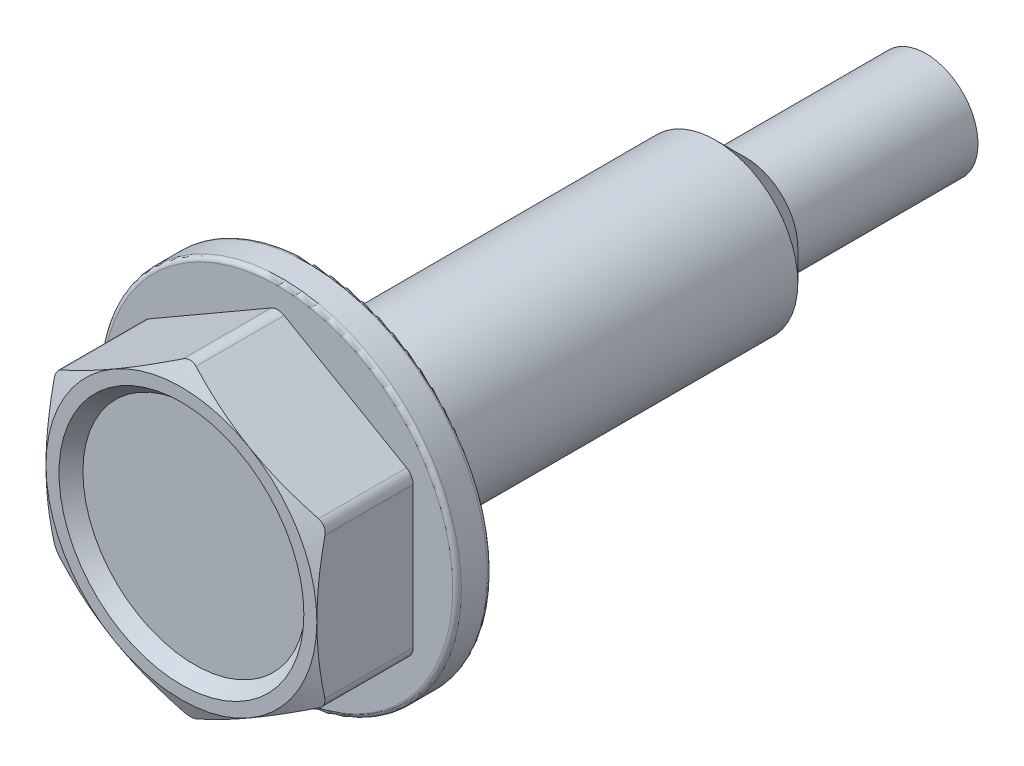
SolidWorks part; units mm, degrees
ref_plane "Front Plane" through (0, 0, 0) normal (0, 0, 1) x (1, 0, 0)
ref_plane "Top Plane" through (0, 0, 0) normal (0, 1, 0) x (1, 0, 0)
ref_plane "Right Plane" through (0, 0, 0) normal (1, 0, 0) x (0, 0, -1)
sketch "Sketch2" plane through (0, 0, 0) normal (0, 0, 1) x (1, 0, 0)
  circle A0 centre (0, 0) radius 2.413
  dimension "screw dia" = 4.826
curve "Helix/Spiral1" pitch 1.5875 height 25.4 radius 2.413 centre (0, 0, 0) axis (0, 0, 1) start towards (0, 1, 0) parameters "TPI LENGTH"=25.4, "PITCH"=1.5875
sketch "Sketch3" plane through (0, 0, 0) normal (1, 0, 0) x (0, 0, -1)
  line L0 (0.113, 2.413) -> (-0.113, 2.413)
  line L1 (-0.113, 2.413) -> (-0.6236, 1.5287)
  line L2 (-0.6236, 1.5287) -> (0.6236, 1.5287)
  line L3 (0.6236, 1.5287) -> (0.113, 2.413)
  line L4 (0, 0) -> (0, 2.413) construction
  line L5 (-0.3683, 1.9709) -> (0.3683, 1.9709) construction
  line L6 (0, 2.413) -> (0, -2.413) construction
  line L7 (0, 2.6088) -> (0.7937, 2.6088) construction
  line L8 (0.7937, 2.6088) -> (0.7938, 1.234) construction
  line L9 (0.7938, 1.234) -> (1.6942, 2.7936) construction
  line L10 (-0.9361, 2.413) -> (-0.9361, 1.5287) construction
  dimension "D1" = 60
  dimension "D2" = 30
  dimension "D3" = 1.3748
  dimension "pitch*.125" = 0.2261
  dimension "D4" = 0.8843
  dimension "pitch*.5" = 0.7366
  dimension "1/2pitch" = 0.7937
sweep "Sweep1" add profiles "Sketch3" path "Helix/Spiral1"
sketch "Sketch4" plane through (0, 0, 0) normal (1, 0, 0) x (0, 0, -1)
  line L0 (-1.9435, 0.508) -> (0.436, 0.508) construction
  line L4 (0.6236, 1.5287) -> (0.113, 2.413)
  line L5 (-0.6236, 1.5287) -> (0.6236, 1.5287)
  line L6 (-0.113, 2.413) -> (-0.6236, 1.5287)
  line L7 (0.113, 2.413) -> (-0.113, 2.413)
  line L8 (0.6236, 1.5287) -> (0.113, 2.413)
  line L9 (-0.6236, 1.5287) -> (0.6236, 1.5287)
  line L10 (-0.113, 2.413) -> (-0.6236, 1.5287)
  line L11 (0.113, 2.413) -> (-0.113, 2.413)
  dimension "D2" = 0.508
  dimension "D1" = 0
revolve "Revolve1" add sketch "Sketch4" angle 360 about L0
sketch "Sketch5" plane through (0, 0, 0) normal (1, 0, 0) x (0, 0, -1)
  line L0 (0, 0) -> (3.5657, 0) construction
  line L2 (0, 0) -> (-26.0236, 0)
  line L3 (0, 0) -> (0, 1.5287)
  line L4 (0, 1.5287) -> (-26.0236, 1.5287)
  line L5 (-26.0236, 0) -> (-26.0236, 1.5287)
revolve "Revolve2" add sketch "Sketch5" angle 360 about L0
sketch "Sketch7" plane through (0, 0, 0) normal (1, 0, 0) x (0, 0, -1)
  line L0 (0, 1.5287) -> (-4.5282, 6.0569)
  line L1 (-4.5282, 6.0569) -> (4.5061, 6.0569)
  line L2 (4.5061, 6.0569) -> (4.5061, 0)
  line L3 (0, 1.5287) -> (0, 0)
  line L4 (0, 0) -> (4.5061, 0)
  line L5 (0, 0) -> (11.6435, 0) construction
  dimension "D1" = 45
revolve "Cut-Revolve1" cut sketch "Sketch7" angle 360 about L5
sketch "Sketch8" plane through (0, 0, 0) normal (1, 0, 0) x (0, 0, -1)
  line L0 (0, 0) -> (6.35, 0)
  line L1 (6.35, 0) -> (5.2796, 1.5287)
  line L2 (5.2796, 1.5287) -> (0, 1.5287)
  line L3 (0, 0) -> (0, 1.5287)
  line L4 (6.35, 0) -> (7.6191, 0) construction
  dimension "D1" = 55
  dimension "DRILL POINT LENGTH" = 6.35
revolve "Revolve3" add sketch "Sketch8" angle 360 about L4
ref_plane "Plane1" through (0, 0, -6.35) normal (0, 0, 1) x (1, 0, 0)
ref_plane "Plane2" through (0.381, 0, 0) normal (1, 0, 0) x (0, 0, -1)
sketch "Sketch9" plane through (0.381, 0, 0) normal (1, 0, 0) x (0, 0, -1)
  line L0 (0, 1.5287) -> (6.35, 0)
  line L1 (6.35, 0) -> (6.35, 4.1453)
  line L2 (0, 1.5287) -> (0, 4.1453)
  line L3 (0, 4.1453) -> (6.35, 4.1453)
extrude "Cut-Extrude2" cut sketch "Sketch9" along normal through all draft 10
pattern_circular "CirPattern1" count 2 over 360 about axis through (0, 0, 0) along (0, 0, 1) of "Cut-Extrude2"
sketch "Sketch10" plane through (0, 0, 0) normal (1, 0, 0) x (0, 0, -1)
  line L1 (-114.3, -8.9189) -> (-12.7, -8.9189)
  line L2 (-114.3, -8.9189) -> (-114.3, 7.151)
  line L3 (-114.3, 7.151) -> (-12.7, 7.151)
  line L4 (-12.7, -8.9189) -> (-12.7, 7.151)
  dimension "D1" = 101.6
  dimension "D2" = 19.05
extrude "Cut-Extrude3" cut sketch "Sketch10" against normal through all and the other way through all
sketch "Sketch11" plane through (0, 0, 12.7) normal (0, 0, 1) x (1, 0, 0)
  circle A0 centre (0, 0) radius 5.2578
  dimension "WASHER DIA" = 10.5156
extrude "Extrude1" add sketch "Sketch11" along normal blind 1.016
sketch "Sketch12" plane through (0, 0, 12.7) normal (0, 0, -1) x (-1, 0, 0)
  line L1 (0, 4.5827) -> (-3.9688, 2.2914)
  line L2 (-3.9688, 2.2914) -> (-3.9688, -2.2914)
  line L3 (-3.9688, -2.2914) -> (0, -4.5827)
  line L4 (0, -4.5827) -> (3.9688, -2.2914)
  line L5 (3.9688, -2.2914) -> (3.9688, 2.2914)
  line L6 (3.9688, 2.2914) -> (0, 4.5827)
  circle A0 centre (0, 0) radius 3.9688 construction
  dimension "HEX HEAD DIA" = 7.9375
sketch "Sketch13" plane through (0, 0, 0) normal (1, 0, 0) x (0, 0, -1)
  line L0 (-16.5354, 0) -> (-12.7, 0)
  line L1 (-12.7, -5.2578) -> (-12.7, 5.2578) construction
  dimension "HEAD HEIGHT" = 3.8354
sweep "Sweep2" add profiles "Sketch12" path "Sketch13"
sketch "Sketch14" plane through (0, 0, 0) normal (1, 0, 0) x (0, 0, -1)
  line L0 (-16.5354, 4.5827) -> (-16.5354, 3.9688)
  line L1 (-16.5354, 3.9688) -> (-16.2491, 4.5827)
  line L2 (-16.2491, 4.5827) -> (-16.5354, 4.5827)
  line L3 (-16.5354, 4.5827) -> (-13.716, 4.5827) construction
  line L4 (-16.5354, 4.5827) -> (-16.5354, 2.2914) construction
  line L8 (-12.7, -3.9688) -> (-12.7, 3.9688) construction
  line L9 (-12.7, -3.9688) -> (-12.7, 3.9688) construction
  dimension "D1" = 25
revolve "Cut-Revolve2" cut sketch "Sketch14" angle 360 about axis through (0, 0, 0) along (0, 0, -1)
sketch "Sketch15" plane through (0, 0, 16.5354) normal (0, 0, 1) x (1, 0, 0)
  arc A6 (1.7939, -3.1071) -> (3.5878, 0) centre (0, 0) ccw
  arc A7 (1.7939, -3.1071) -> (3.5878, 0) centre (0, 0) ccw
  arc A8 (3.5878, 0) -> (1.7939, 3.1071) centre (0, 0) ccw
  arc A9 (3.5878, 0) -> (1.7939, 3.1071) centre (0, 0) ccw
  arc A10 (1.7939, 3.1071) -> (-1.7939, 3.1071) centre (0, 0) ccw
  arc A11 (1.7939, 3.1071) -> (-1.7939, 3.1071) centre (0, 0) ccw
  arc A12 (-1.7939, 3.1071) -> (-3.5878, 0) centre (0, 0) ccw
  arc A13 (-1.7939, 3.1071) -> (-3.5878, 0) centre (0, 0) ccw
  arc A14 (-3.5878, 0) -> (-1.7939, -3.1071) centre (0, 0) ccw
  arc A15 (-3.5878, 0) -> (-1.7939, -3.1071) centre (0, 0) ccw
  arc A16 (-1.7939, -3.1071) -> (1.7939, -3.1071) centre (0, 0) ccw
  arc A17 (-1.7939, -3.1071) -> (1.7939, -3.1071) centre (0, 0) ccw
  dimension "D1" = 0.381
extrude "Cut-Extrude4" cut sketch "Sketch15" against normal blind 0.381 draft 40
fillet "Fillet1" radius 0.381 6 edges at (-3.9688, -2.2914, 14.9826) (0, -4.5827, 14.9826) (3.9688, -2.2914, 14.9826) (-3.9688, 2.2914, 14.9826) (0, 4.5827, 14.9826) (3.9688, 2.2914, 14.9826)
fillet "Fillet3" radius 0.127 2 edges at (5.2578, 0, 12.7) (5.2578, 0, 13.716)
split line "Split Line1"
sketch "Sketch16" plane through (0, 0, 0) normal (1, 0, 0) x (0, 0, -1)
  line L0 (-13.0118, 0) -> (-13.0118, 1.5287) construction
  line L1 (0, 0) -> (-26.0236, 0) construction
  line L2 (0, 1.5287) -> (-26.0236, 1.5287) construction
sketch "Sketch17" plane through (0, 0, 0) normal (0, 1, 0) x (1, 0, 0)
  line L0 (0, -13.2384) -> (0, 6.35)
  line L1 (0, 6.35) -> (-1.5287, 5.2796) construction
  line L2 (0, 6.35) -> (-1.5287, 5.2796)
  line L3 (-1.5287, 5.2796) -> (-1.5287, 0) construction
  line L4 (-1.5287, 5.2796) -> (-1.5287, 0)
  line L5 (-1.5287, 0) -> (-2.1756, -0.6469) construction
  line L6 (-1.5287, 0) -> (-2.413, -0.8843)
  line L7 (-2.413, -1.8713) -> (-2.413, -2.0974) construction
  line L8 (-2.413, -0.8843) -> (-2.413, -13.2384)
  line L9 (-2.413, -13.2384) -> (0, -13.2384)
  line L10 (0, -13.2384) -> (0, -21.0494) construction
revolve "Revolve4" add sketch "Sketch17" angle 360 about L10
